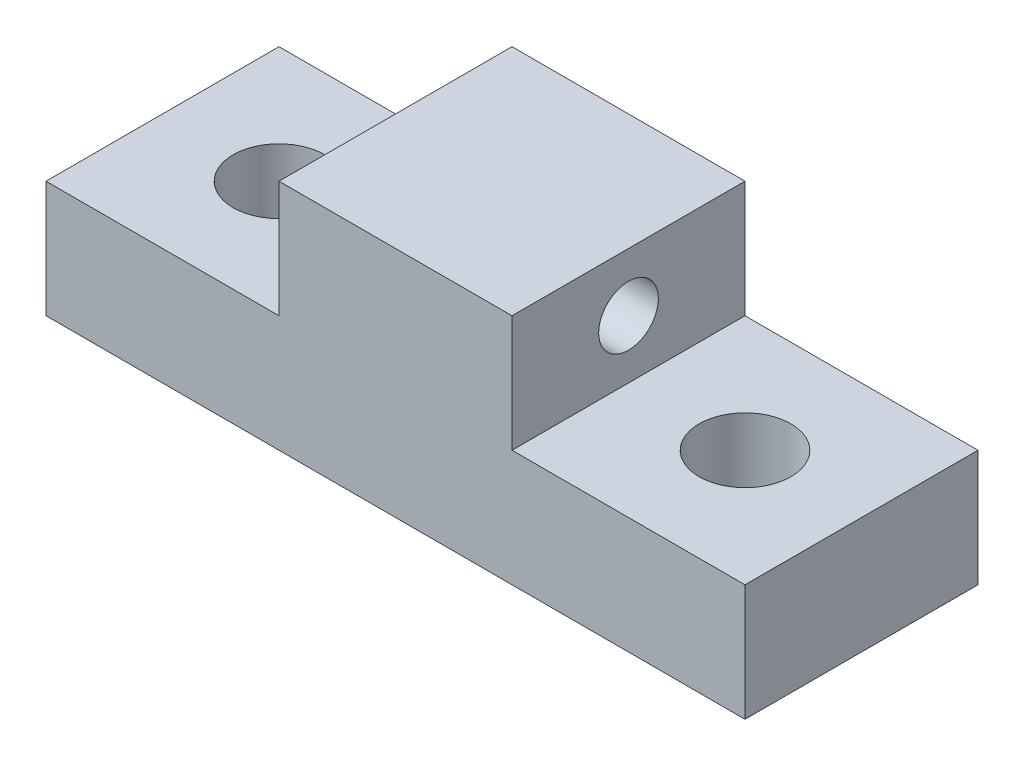
SolidWorks part; units mm, degrees
material "Bambu PAHT-CF"
ref_plane "Front Plane" through (0, 0, 0) normal (0, 0, 1) x (1, 0, 0)
ref_plane "Top Plane" through (0, 0, 0) normal (0, 1, 0) x (1, 0, 0)
ref_plane "Right Plane" through (0, 0, 0) normal (1, 0, 0) x (0, 0, -1)
sketch "Sketch1" plane through (0, 0, 0) normal (0, 1, 0) x (1, 0, 0)
  line L0 (-25.4, 0) -> (0, 0) construction
  line L1 (-38.1, -12.7) -> (38.1, -12.7)
  line L2 (-38.1, -12.7) -> (-38.1, 12.7)
  line L3 (-38.1, 12.7) -> (38.1, 12.7)
  line L4 (38.1, -12.7) -> (38.1, 12.7)
  line L5 (-38.1, -12.7) -> (38.1, 12.7) construction
  line L6 (-38.1, 12.7) -> (38.1, -12.7) construction
  line L7 (-25.4, 0) -> (-38.1, 0) construction
  line L8 (-38.1, -12.7) -> (-12.7, -12.7)
  line L9 (-38.1, -12.7) -> (-38.1, 12.7)
  line L10 (-38.1, 12.7) -> (-12.7, 12.7)
  line L11 (-12.7, -12.7) -> (-12.7, 12.7) construction
  line L12 (-25.4, 0) -> (-12.7, 0) construction
  line L13 (0, -12.7) -> (0, 12.7) construction
  circle A0 centre (-25.4, 0) radius 3.2512
  circle A1 centre (25.4, 0) radius 3.2512
  point P0 (0, 0)
  dimension "D3" = 6.5024
  dimension "D1" = 25.4
  dimension "D2" = 76.2
  dimension "D4" = 25.4
extrude "Boss-Extrude1" add sketch "Sketch1" along normal blind 12.7 contours L1 L4 L3 L2 A0 A1 region at (0, 0, 0)
sketch "Sketch2" plane through (0, 12.7, 0) normal (0, 1, 0) x (1, 0, 0)
  line L0 (-38.1, 12.7) -> (38.1, 12.7) construction
  line L1 (-12.7, -12.7) -> (12.7, -12.7)
  line L2 (-12.7, -12.7) -> (-12.7, 12.7)
  line L3 (-12.7, 12.7) -> (12.7, 12.7)
  line L4 (12.7, -12.7) -> (12.7, 12.7)
  line L5 (-12.7, -12.7) -> (12.7, 12.7) construction
  line L6 (-12.7, 12.7) -> (12.7, -12.7) construction
  point P0 (0, 0)
  dimension "D1" = 25.4
extrude "Boss-Extrude2" add sketch "Sketch2" along normal blind 12.7
sketch "Sketch3" plane through (-12.7, 0, 0) normal (-1, 0, 0) x (0, 0, 1)
  line L0 (-12.7, 12.7) -> (12.7, 25.4) construction
  line L1 (12.7, 25.4) -> (12.7, 12.7) construction
  line L2 (12.7, 12.7) -> (-12.7, 25.4) construction
  line L3 (-12.7, 25.4) -> (-12.7, 12.7) construction
  circle A0 centre (0, 19.05) radius 3.2512
  dimension "D1" = 6.5024
extrude "Cut-Extrude1" cut sketch "Sketch3" against normal blind 43.7
sketch "Sketch4" plane through (0, 12.7, 0) normal (0, 1, 0) x (1, 0, 0)
  circle A0 centre (-25.4, 0) radius 5
  circle A1 centre (25.4, 0) radius 5
  point P4 (0, 0)
  dimension "D1" = 10
  dimension "D2" = 10
  dimension "D3" = 25.4
  dimension "D4" = 25.4
extrude "Cut-Extrude2" cut sketch "Sketch4" against normal blind 7.35
